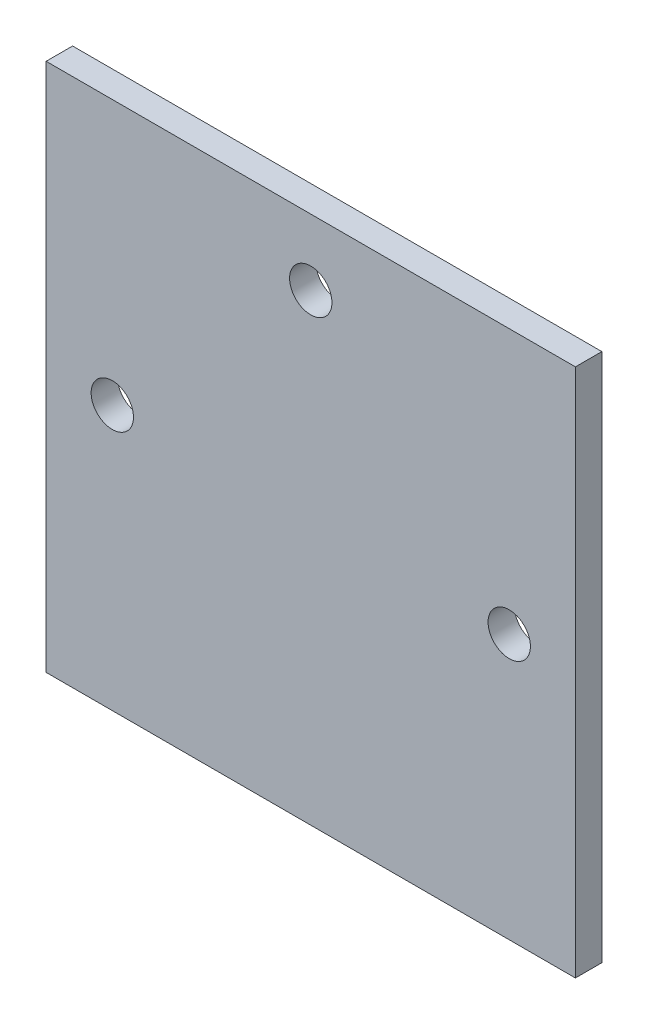
SolidWorks part; units mm, degrees
material "Простая углеродистая сталь"
ref_plane "Спереди" through (0, 0, 0) normal (0, 0, 1) x (1, 0, 0)
ref_plane "Сверху" through (0, 0, 0) normal (0, 1, 0) x (1, 0, 0)
ref_plane "Справа" through (0, 0, 0) normal (1, 0, 0) x (0, 0, -1)
sketch "Эскиз1" plane through (0, 0, 0) normal (0, 0, 1) x (1, 0, 0)
  line L1 (0, 0) -> (200, 0)
  line L2 (0, 0) -> (0, -200)
  line L3 (0, -200) -> (200, -200)
  line L4 (200, 0) -> (200, -200)
  line L5 (100, -200) -> (100, 0) construction
  line L6 (0, -100) -> (200, -100) construction
  point P192 (100, -100)
  dimension "D1" = 200
  dimension "D2" = 200
base flange "Базовая кромка1" sketch "Эскиз1" thickness 10 reverse thickness direction no parameters "D1"=0.8
sketch "Эскиз2" plane through (0, 0, -10) normal (0, 0, -1) x (-1, 0, 0)
  circle A0 centre (-63.2969, -37.2697) radius 7
  dimension "D1" = 14
sketch "Эскиз3" plane through (0, 0, -10) normal (0, 0, -1) x (-1, 0, 0)
  line L0 (-200, -200) -> (-200, 0) construction
  line L1 (0, -200) -> (-200, -200) construction
  line L2 (-200, 0) -> (0, 0) construction
  line L3 (-100, -200) -> (-100, -120.6294) construction
  circle A0 centre (-175, -100) radius 8
  circle A1 centre (-100, -25) radius 8
  circle A2 centre (-25, -100) radius 8
  dimension "D1" = 16
  dimension "D2" = 25
  dimension "D3" = 100
  dimension "D4" = 25
  dimension "D5" = 100
extrude "Вырез-Вытянуть1" cut sketch "Эскиз3" against normal blind 10 normal cut yes
sketch "Сгиб-Линии1" [suppressed] plane through (0, 0, 0) normal (0, 1, 0) x (1, 0, 0)
sketch "Граничная рамка1" [suppressed] plane through (0, 0, 0) normal (0, 1, 0) x (1, 0, 0)
sheet metal parameters "Листовой металл1" thickness 10 parameters "D1"=0.8
flat pattern "Развертка1" [suppressed]
sketch "Сгиб-Линии2" plane through (0, 0, 0) normal (0, 1, 0) x (1, 0, 0)
sketch "Граничная рамка2" [suppressed] plane through (0, 0, 0) normal (0, 1, 0) x (1, 0, 0)
sheet metal parameters "Листовой металл2" thickness 10 parameters "D1"=0.8
flat pattern "Развертка1" [suppressed]
sketch "Сгиб-Линии2" plane through (0, 0, 0) normal (0, 1, 0) x (1, 0, 0)
sketch3d "Граничная рамка2" [suppressed]
  line L0 (0, -200, 0) -> (200, -200, 0) construction
  line L1 (0, 0, 0) -> (200, 0, 0) construction
  line L2 (0, -200, 0) -> (0, 0, 0) construction
  line L3 (200, -200, 0) -> (200, 0, 0) construction
sketch "Эскиз2-1" plane through (0, 0, -10) normal (0, 0, -1) x (-1, 0, 0)
  circle A0 centre (-63.2969, -37.2697) radius 7
  dimension "D1" = 14
